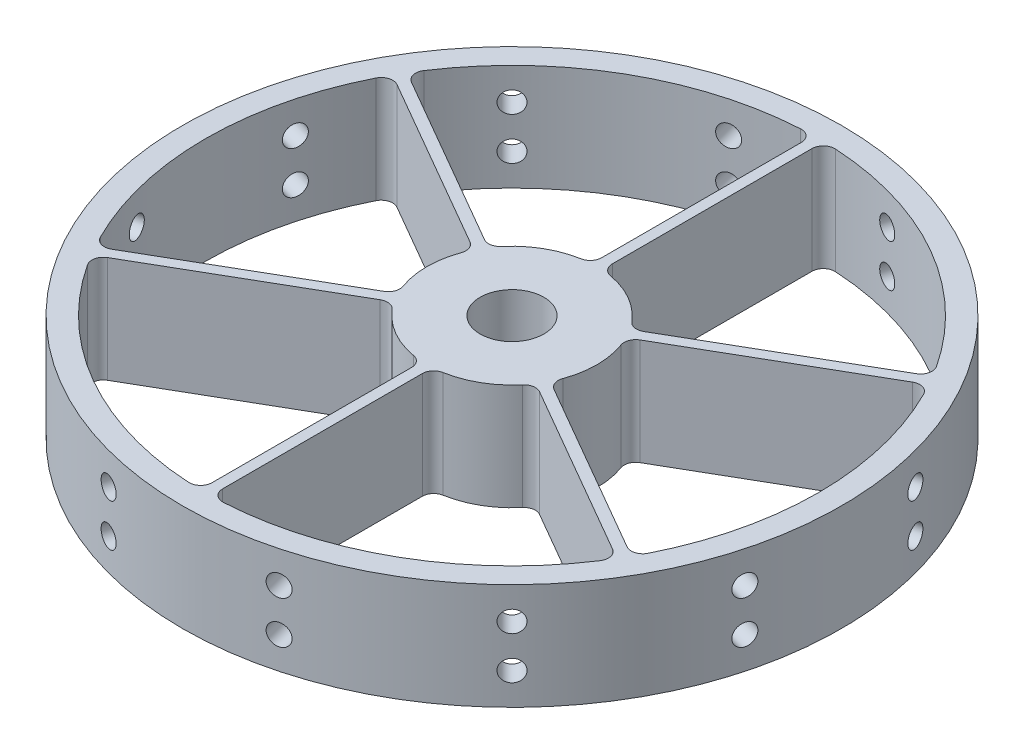
SolidWorks part; units mm, degrees
material "6061-T6 (SS)"
ref_plane "Front Plane" through (0, 0, 0) normal (0, 0, 1) x (1, 0, 0)
ref_plane "Top Plane" through (0, 0, 0) normal (0, 1, 0) x (1, 0, 0)
ref_plane "Right Plane" through (0, 0, 0) normal (1, 0, 0) x (0, 0, -1)
sketch "ring" plane through (0, 0, 0) normal (0, 1, 0) x (1, 0, 0)
  line L0 (0, 25.4) -> (0, 91.567) construction
  line L1 (25.4, 0) -> (91.567, 0) construction
  line L2 (0, -25.4) -> (0, -91.567) construction
  line L3 (-25.4, 0) -> (-91.567, 0) construction
  line L4 (-1.5883, 25.3503) -> (-1.5883, 91.5532)
  line L5 (1.5867, 25.3504) -> (1.5867, 91.5533)
  circle A0 centre (0, 0) radius 25.4
  circle A1 centre (0, 0) radius 91.567
  circle A2 centre (0, 0) radius 98.425
  dimension "D1" = 50.8
  dimension "D3" = 196.85
  dimension "D2" = 6.858
  dimension "D4" = 1.5867
  dimension "D5" = 3.175
sketch "beam" plane through (0, 0, 0) normal (0, 1, 0) x (1, 0, 0)
  line L1 (1.5875, 25.3503) -> (1.5875, 97.7771)
  line L3 (-1.5875, 25.3503) -> (-1.5875, 97.7771)
  line L4 (0, 25.4) -> (0, 91.567) construction
  circle A2 centre (0, 0) radius 25.4 construction
  circle A4 centre (0, 0) radius 97.79 construction
  arc A5 (1.5875, 25.3503) -> (-1.5875, 25.3503) centre (0, 0) ccw
  arc A6 (1.5875, 97.7771) -> (-1.5875, 97.7771) centre (0, 0) ccw
  dimension "D3" = 50.8
  dimension "D4" = 195.58
  dimension "D1" = 1.5875
  dimension "D2" = 3.175
extrude "Boss-Extrude1" add sketch "ring" along normal mid plane 31.75 contours A2 A1 | A0 region at (0, 0, 0) region at (-95.6411, 0, 0)
ref_axis "Axis1" through (0, 21.8355, 0) along (0, -1, 0)
extrude "Boss-Extrude2" add sketch "beam" along normal mid plane 31.75 contours L1 A6 L3 A5
ref_plane "Plane1" through (0, 0, 0) normal (-0.2588, 0, -0.9659) x (0, -1, 0)
pattern_circular "CirPattern1" count 6 over 360 about axis through (0, 21.8355, 0) along (0, -1, 0) of "Boss-Extrude2"
sketch "Sketch3" plane through (0, 0, 0) normal (0, 1, 0) x (1, 0, 0)
  circle A0 centre (0, 0) radius 9.525
  dimension "D1" = 19.05
split line "Split Line1"
sketch "Sketch4" plane through (0, 0, 0) normal (0, 1, 0) x (1, 0, 0)
  line L0 (-21.1603, 14.05) -> (-78.4937, 47.1514) construction
  line L1 (104.5183, -60.3437) -> (119.2332, -68.8393)
  line L2 (-21.1603, 14.05) -> (-78.4937, 47.1514) construction
split line "Split Line2" [suppressed]
fillet "Fillet1" radius 3.429 24 edges at (-80.0812, 0, 44.4018) (-80.0812, 0, -44.4018) (-22.7478, 0, 11.3004) (-22.7478, 0, -11.3004) (-21.1603, 0, -14.05) (-1.5875, 0, -25.3503) (-78.4937, 0, -47.1514) (-1.5875, 0, -91.5532) (1.5875, 0, -91.5532) (78.4937, 0, -47.1514) (21.1603, 0, -14.05) (1.5875, 0, -25.3503) (22.7478, 0, 11.3004) (22.7478, 0, -11.3004) (80.0812, 0, 44.4018) (80.0812, 0, -44.4018) (1.5875, 0, 91.5532) (1.5875, 0, 25.3503) (21.1603, 0, 14.05) (78.4937, 0, 47.1514) (-1.5875, 0, 91.5532) (-1.5875, 0, 25.3503) (-21.1603, 0, 14.05) (-78.4937, 0, 47.1514)
sketch "Sketch8" plane through (0, 15.875, 0) normal (0, 1, 0) x (1, 0, 0)
  circle A0 centre (0, 0) radius 9.525
  circle A1 centre (0, 0) radius 9.525 construction
extrude "Cut-Extrude1" cut sketch "Sketch8" against normal through all
sketch "Sketch10" plane through (0, 0, 0) normal (-0.2588, 0, -0.9659) x (0, -1, 0)
  line L1 (15.875, -9.525) -> (15.875, 9.525) construction
  circle A1 centre (-6.35, 0) radius 3.175
  circle A2 centre (6.35, 0) radius 3.175
  dimension "D1" = 6.35
  dimension "D2" = 6.35
  dimension "D3" = 12.7
  dimension "D4" = 9.525
extrude "Cut-Extrude2" cut sketch "Sketch10" along normal through all from offset 38.1
pattern_circular "CirPattern3" count 12 over 360 about axis through (0, 15.875, 0) along (0, -1, 0) of "Cut-Extrude2" reverse direction yes
equation "\"H\"= 1.25"
equation "\"D1@Boss-Extrude2\"=\"H\""
equation "\"D\"= 2"
equation "\"a\"= .125"
equation "\"T\"= .27"
equation "\"N\"= 6"
equation "\"D1@CirPattern1\"=\"N\""
equation "\"D1@Boss-Extrude1\"=\"H\""
equation "\"D2@beam\"=\"a\""
equation "\"D1@beam\"=\"a\"/2"
equation "\"D2@ring\"=\"T\""
equation "\"D1@ring\"=\"D\""
equation "\"rodD\"= 0.75"
equation "\"D1@Sketch3\"=\"rodD\""
